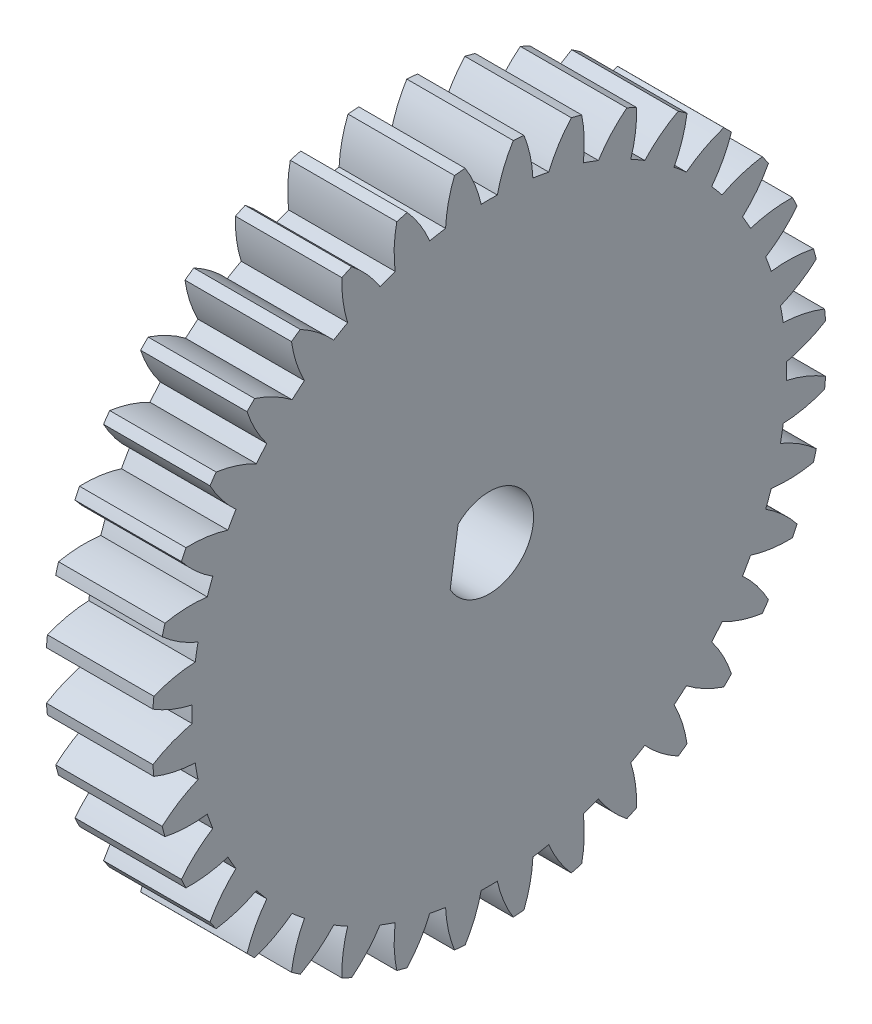
SolidWorks part; units mm, degrees
ref_plane "Plane1" through (0, 0, 0) normal (0, 0, 1) x (1, 0, 0)
ref_plane "Plane2" through (0, 0, 0) normal (0, 1, 0) x (1, 0, 0)
ref_plane "Plane3" through (0, 0, 0) normal (1, 0, 0) x (0, 0, -1)
sketch "HoldingSke" plane through (0, 0, 0) normal (0, 1, 0) x (1, 0, 0)
  line L0 (0, 0) -> (0.809, -0.5878)
  line L1 (-15, 0) -> (100, 0) construction
  line L2 (0, 0) -> (-2.1039, 2.3779)
  line L3 (0, 0) -> (-11.863, 4.5341)
  line L4 (0, 0) -> (6.9867, 5.0761)
  line L5 (0, 0) -> (-46.8476, -17.4728)
  line L6 (0, 0) -> (-4.9738, -3.3558)
  line L7 (-2.1039, 2.3779) -> (8.6586, 51.2059)
  line L8 (-76.2, 54.61) -> (-76.1, 54.61)
  line L9 (-71.009, 38.7566) -> (-53.1078, 45.2721)
  line L10 (-76.2, 71.12) -> (104.1128, 71.12)
  line L11 (0, 0) -> (-6, 0)
  line L12 (-76.2, 101.6) -> (-76.162, 101.6)
  line L13 (24.9733, 27.94) -> (52.9518, 28.4284)
  line L14 (24.9733, 27.94) -> (24.9743, 27.94)
  line L15 (24.9733, 27.94) -> (100.4006, 29.5858)
  line L16 (-63.627, -1) -> (-12.827, -1)
  circle A0 centre (0, 0) radius 0.4
  circle A1 centre (0, 0) radius 16.749
  circle A2 centre (0, 0) radius 37.5
  circle A3 centre (0, 0) radius 0.4
  dimension "MHD" = 33.498
  dimension "Hub_dia" = 75
  dimension "Bore" = 0.8
  dimension "MBD" = 0.8
  dimension "Num_teeth" = 36
  dimension "Pitch" = 1
  dimension "Overall_len" = 50
  dimension "Show_teeth" = 36
  dimension "Thickness" = 6
  dimension "OAL" = 50.0001
  dimension "T_dim" = 0.1
  dimension "Ap" = 20
  dimension "H" = 19.05
  dimension "Pitch_radius" = 180.3128
  dimension "Width" = 6
  dimension "Backlash" = 0.038
  dimension "Addendum_fac" = 1
  dimension "Dedendum_fac" = 1.25
  dimension "Clearance_fac" = 0.25
  dimension "Dedendum_add" = 0.001
  dimension "Module" = 1
sketch "BasProSke" plane through (0, 0, 0) normal (0, 1, 0) x (1, 0, 0)
  line L0 (-10, 0) -> (60, 0) construction
  line L1 (0, 0) -> (0, 19)
  line L2 (0, 0) -> (6, 0)
  line L3 (6, 0) -> (6, 19)
  line L4 (6, 19) -> (0, 19)
  dimension "Thickness" = 6
  dimension "Diameter" = 38
revolve "Base-Revolve" add sketch "BasProSke" angle 360 about L0
sketch "TooCutSke" plane through (0, 0, 0) normal (1, 0, 0) x (0, 0, -1)
  line L1 (0, 0) -> (0, 107) construction
  line L2 (0, 0) -> (-0.8516, 17.9798) construction
  line L3 (0, 0) -> (-3.1351, 35.8344) construction
  line L4 (-0.8516, 17.9798) -> (-1.5676, 17.9172) construction
  arc A0 (0.4547, 16.7428) -> (-0.4547, 16.7428) centre (0, 0) ccw
  arc A1 (1.3689, 18.9761) -> (-1.3689, 18.9761) centre (0, 0) ccw
  circle A2 centre (0, 0) radius 18 construction
  circle A3 centre (0, 0) radius 16.9145 construction
  arc A4 (-0.4547, 16.7428) -> (-1.3689, 18.9761) centre (-7.4808, 15.1702) ccw
  arc A5 (1.3689, 18.9761) -> (0.4547, 16.7428) centre (7.4808, 15.1702) ccw
  dimension "Root_dia" = 33.498
  dimension "Overcut_dia" = 38.0508
  dimension "Pitch_dia" = 36
  dimension "Base_dia" = 33.8289
  dimension "Flank_rad" = 7.2
  dimension "Half_ang" = 5
  dimension "Half_CT" = 0.7186
extrude "ToothCut" cut sketch "TooCutSke" along normal through all
fillet "Breaks" [suppressed] radius 0.02 tangent propagation no
fillet "RootFillets" [suppressed] radius 0.251
pattern_circular "TeethCuts" count 36 over 360 about axis through (-10, 0, 0) along (1, 0, 0) of "ToothCut", "RootFillets", "Breaks"
sketch "HubNeaOneSke" plane through (0, 0, 0) normal (-1, 0, 0) x (0, 0, 1)
  circle A0 centre (0, 0) radius 16.749
  dimension "Diameter" = 33.498
extrude "HubNearOne" [suppressed] add sketch "HubNeaOneSke" along normal blind 44.0001
sketch "HubNeaBotSke" plane through (0, 0, 0) normal (-1, 0, 0) x (0, 0, 1)
  circle A0 centre (0, 0) radius 16.749
  dimension "Diameter" = 33.498
extrude "HubNearBoth" [suppressed] add sketch "HubNeaBotSke" along normal blind 22
ref_plane "FarPln" through (6, 0, 0) normal (1, 0, 0) x (0, 0, -1)
sketch "HubFarSke" plane through (6, 0, 0) normal (1, 0, 0) x (0, 0, -1)
  circle A0 centre (0, 0) radius 16.749
  dimension "Diameter" = 33.498
extrude "HubFar" [suppressed] add sketch "HubFarSke" along normal blind 22
sketch "BorSke" plane through (0, 0, 0) normal (1, 0, 0) x (0, 0, -1)
  line L0 (-2.2004, -1.1866) -> (-1.7553, 1.7802)
  arc A0 (-2.2004, -1.1866) -> (-1.7553, 1.7802) centre (0, 0) ccw
  dimension "D1" = 3
  dimension "D2" = 2.5
extrude "Bore" cut sketch "BorSke" along normal mid plane 100.0001
sketch "KeySke" plane through (0, 0, 0) normal (1, 0, 0) x (0, 0, -1)
  line L0 (-0.05, 0) -> (-0.05, 0.5)
  line L1 (-0.05, 0.5) -> (0.05, 0.5)
  line L2 (0.05, 0.5) -> (0.05, 0)
  line L3 (0, 0) -> (0, 34) construction
  line L4 (-0.05, 0) -> (0.05, 0)
  dimension "Offset" = 0.5
  dimension "Width" = 0.1
extrude "Keyway" [suppressed] cut sketch "KeySke" along normal mid plane 100.0001
pattern_circular "Keyway2" [suppressed] count 2 every 90 about axis through (-10, 0, 0) along (1, 0, 0) reverse direction yes
equation "' \"Module@HoldingSke\" = 6.35"
equation "' \"Num_teeth@HoldingSke\" = 12"
equation "' \"Ap@HoldingSke\" =  20"
equation "' \"Ap@HoldingSke\" = 20"
equation "' \"Width@HoldingSke\" = 0.5 * 25.4"
equation "' \"Hub_dia@HoldingSke\"= 1 * 25.4"
equation "' \"Hub_dia@HoldingSke\" = 1 * 25.4"
equation "' \"Overall_len@HoldingSke\" = 1.0 * 25.4"
equation "' \"Bore@HoldingSke\" = 0.75 * 25.4"
equation "' \"T_dim@HoldingSke\" = 0.1 * 25.4"
equation "' \"Width@KeySke\" = 0.25 * 25.4"
equation "' \"Show_teeth@HoldingSke\" = 13"
equation "' \"Backlash@HoldingSke\" = 0.009 * 25.4"
equation "' \"Addendum_fac@HoldingSke\" = 1.0"
equation "' \"Dedendum_fac@HoldingSke\" = 1.25"
equation "' \"Dedendum_add@HoldingSke\" = 0.00005 * 25.4"
equation "' \"Clearance_fac@HoldingSke\" = 0.25"
equation "\"Pitch@HoldingSke\" = 1 / \"Module@HoldingSke\""
equation "\"Overcut_dia@TooCutSke\" = (\"Num_teeth@HoldingSke\" + 2 * \"Addendum_fac@HoldingSke\") / \"Pitch@HoldingSke\" + 0.002 * 25.4"
equation "\"Pitch_dia@TooCutSke\" = \"Num_teeth@HoldingSke\" / \"Pitch@HoldingSke\""
equation "\"Base_dia@TooCutSke\" = \"Num_teeth@HoldingSke\" / \"Pitch@HoldingSke\" * cos((\"Ap@HoldingSke\"  * 3.14159265 / 180))"
equation "\"Root_dia@TooCutSke\" = (\"Num_teeth@HoldingSke\" + 2) / \"Pitch@HoldingSke\" - 2 * (\"Addendum_fac@HoldingSke\" + \"Dedendum_fac@HoldingSke\") / \"Pitch@HoldingSke\" - \"Dedendum_add@HoldingSke\" * 2"
equation "\"Half_ang@TooCutSke\" = 180 / \"Num_teeth@HoldingSke\""
equation "\"Half_CT@TooCutSke\" = \"Num_teeth@HoldingSke\" / \"Pitch@HoldingSke\" * sin((3.14159265 / 2 / \"Num_teeth@HoldingSke\")) / 2 - 7 * \"Backlash@HoldingSke\" / 4"
equation "\"Flank_rad@TooCutSke\" = \"Num_teeth@HoldingSke\" / \"Pitch@HoldingSke\" / 5"
equation "\"Radius@RootFillets\" = \"Clearance_fac@HoldingSke\" / \"Pitch@HoldingSke\" + \"Dedendum_add@HoldingSke\""
equation "\"Break_rad@Breaks\" = 0.02 / \"Pitch@HoldingSke\""
equation "\"Thickness@HoldingSke\" = \"Width@HoldingSke\""
equation "\"OAL@HoldingSke\" = \"Thickness@HoldingSke\""
equation "\"MHD@HoldingSke\" = (\"Num_teeth@HoldingSke\" + 2) / \"Pitch@HoldingSke\" - 2 * (\"Addendum_fac@HoldingSke\" + \"Dedendum_fac@HoldingSke\")  / \"Pitch@HoldingSke\" - \"Dedendum_add@HoldingSke\" * 2"
equation "\"MBD@HoldingSke\" = (\"Num_teeth@HoldingSke\" + 2) / \"Pitch@HoldingSke\" - 2 * (\"Addendum_fac@HoldingSke\" + \"Dedendum_fac@HoldingSke\")  / \"Pitch@HoldingSke\" - \"Dedendum_add@HoldingSke\" * 2 - 0.002 * 25.4"
equation "\"MHD@HoldingSke\" = ((sgn( \"MHD@HoldingSke\" - \"Hub_dia@HoldingSke\" )-1)*( \"MHD@HoldingSke\" - \"Hub_dia@HoldingSke\" ))/-2+ \"Hub_dia@HoldingSke\""
equation "\"MBD@HoldingSke\" = ((sgn( \"MBD@HoldingSke\" - \"Bore@HoldingSke\" )-1)*( \"MBD@HoldingSke\" - \"Bore@HoldingSke\" ))/-2+ \"Bore@HoldingSke\""
equation "\"OAL@HoldingSke\" = ((sgn( \"OAL@HoldingSke\" - \"Overall_len@HoldingSke\" )+1)*( \"OAL@HoldingSke\" - \"Overall_len@HoldingSke\" ))/2 + \"Overall_len@HoldingSke\" + 0.000002 * 25.4"
equation "\"Num_teeth@TeethCuts\" = int( \"Show_teeth@HoldingSke\" ) + 1"
equation "\"Num_teeth@TeethCuts\" = ((sgn( \"Num_teeth@TeethCuts\" - \"Num_teeth@HoldingSke\" )-1)*( \"Num_teeth@TeethCuts\" - \"Num_teeth@HoldingSke\" ))/-2+ \"Num_teeth@HoldingSke\""
equation "\"Num_teeth@TeethCuts\" = ((sgn( \"Num_teeth@TeethCuts\" - 2.0)+1)*( \"Num_teeth@TeethCuts\" - 2.0))/2 +2.0"
equation "\"Angle@TeethCuts\" = 360.0 / \"Num_teeth@HoldingSke\""
equation "\"Diameter@BasProSke\" = (\"Num_teeth@HoldingSke\" + 2 * \"Addendum_fac@HoldingSke\") / \"Pitch@HoldingSke\""
equation "\"Thickness@BasProSke\"  = \"Thickness@HoldingSke\""
equation "' \"Fillet_rad@BasProSke\" =  \"Thickness@HoldingSke\" * 0.05"
equation "' \"Fillet_rad@BasProSke\" = \"Thickness@HoldingSke\" * 0.05"
equation "\"MHD@HoldingSke\" = ((sgn( \"MHD@HoldingSke\" - \"Root_dia@TooCutSke\" )-1)*( \"MHD@HoldingSke\" - \"Root_dia@TooCutSke\" ))/-2+ \"Root_dia@TooCutSke\""
equation "\"Diameter@HubNeaOneSke\" = \"MHD@HoldingSke\""
equation "\"Length@HubNearOne\" = \"OAL@HoldingSke\" - \"Thickness@BasProSke\""
equation "\"Diameter@HubNeaBotSke\" = \"MHD@HoldingSke\""
equation "\"Length@HubNearBoth\" = ( \"OAL@HoldingSke\" - \"Thickness@BasProSke\" ) / 2.0"
equation "\"Thickness@FarPln\" = \"Thickness@BasProSke\""
equation "\"Diameter@HubFarSke\" = \"MHD@HoldingSke\""
equation "\"Length@HubFar\" = ( \"OAL@HoldingSke\" - \"Thickness@BasProSke\" ) / 2.0"
equation "\"D1@Bore\" = \"OAL@HoldingSke\" * 2.0"
equation "\"D1@Keyway\" = \"OAL@HoldingSke\" * 2.0"
equation "\"Offset@KeySke\" = \"T_dim@HoldingSke\" + \"MBD@HoldingSke\" / 2.0"
